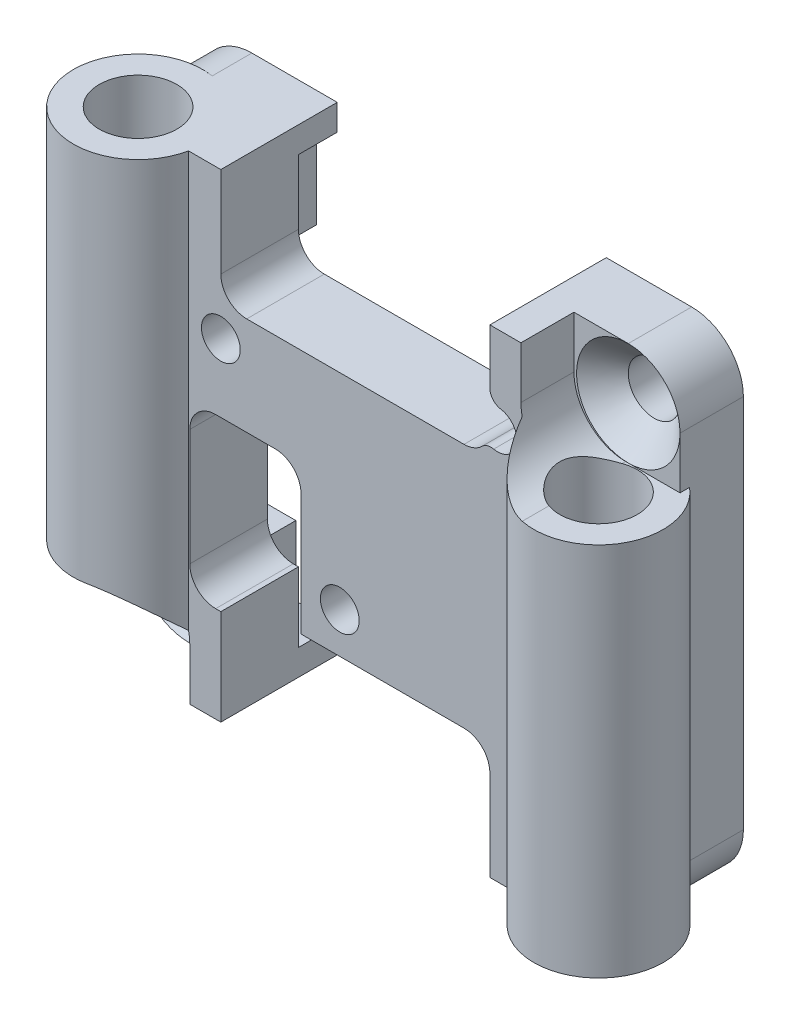
SolidWorks part; units mm, degrees
ref_plane "Top Plane" through (0, 0, 0) normal (0, 0, 1) x (1, 0, 0)
ref_plane "Right Plane" through (0, 0, 0) normal (0, 1, 0) x (1, 0, 0)
ref_plane "Front Plane" through (0, 0, 0) normal (1, 0, 0) x (0, 0, -1)
sketch "Sketch1" plane through (0, 0, 0) normal (0, 0, 1) x (1, 0, 0)
  line L1 (2, 0) -> (5.3, 0)
  line L2 (0, 2) -> (0, 16.5)
  line L3 (2, 18.5) -> (5.3, 18.5)
  line L4 (21, 2) -> (21, 16.5)
  line L5 (20, 2) -> (20, 16.5) construction
  line L6 (1, 3.7) -> (1, 14)
  line L7 (4.5, 17.5) -> (5.3, 17.5)
  line L8 (20, 2) -> (20, 14)
  line L9 (3.7, 1) -> (5.3, 1)
  line L10 (5.3, 0) -> (5.3, 1)
  line L11 (5.3, 17.5) -> (5.3, 18.5)
  line L12 (15.7, 0) -> (15.7, 1)
  line L13 (16.5, 17.5) -> (16.5, 14)
  line L14 (15.7, 17.5) -> (15.7, 18.5)
  line L15 (16.5, 14) -> (20, 14)
  line L16 (1, 3.7) -> (3.7, 3.7)
  line L17 (3.7, 3.7) -> (3.7, 1)
  line L18 (1, 14) -> (4.5, 14)
  line L19 (4.5, 14) -> (4.5, 17.5)
  line L20 (15.7, 18.5) -> (19, 18.5)
  line L21 (15.7, 17.5) -> (16.5, 17.5)
  line L22 (5.3, 18.5) -> (15.7, 18.5) construction
  line L23 (2, 18.5) -> (19, 18.5) construction
  line L24 (15.7, 1) -> (19, 1)
  line L25 (5.3, 17.5) -> (15.7, 17.5) construction
  line L26 (2, 17.5) -> (19, 17.5) construction
  line L27 (15.7, 0) -> (19, 0)
  line L28 (5.3, 1) -> (15.7, 1) construction
  line L29 (2, 1) -> (19, 1) construction
  line L31 (5.3, 0) -> (15.7, 0) construction
  line L32 (2, 0) -> (19, 0) construction
  line L33 (1, 2) -> (1, 16.5) construction
  arc A0 (2, 0) -> (0, 2) centre (2, 2) cw
  arc A1 (19, 0) -> (21, 2) centre (19, 2) ccw
  arc A2 (19, 18.5) -> (21, 16.5) centre (19, 16.5) cw
  arc A3 (0, 16.5) -> (2, 18.5) centre (2, 16.5) cw
  arc A6 (19, 1) -> (20, 2) centre (19, 2) ccw
  arc A9 (2, 1) -> (1, 2) centre (2, 2) cw construction
  arc A10 (19, 17.5) -> (20, 16.5) centre (19, 16.5) cw construction
  arc A11 (1, 16.5) -> (2, 17.5) centre (2, 16.5) cw construction
  point P7 (0, 0)
  point P10 (21, 0)
  point P15 (0, 18.5)
  dimension "D3" = 2
  dimension "D6" = 3.5
  dimension "D1" = 18.5
  dimension "D2" = 21
  dimension "D5" = 2.7
  dimension "D7" = 10.4
  dimension "D4" = 1
extrude "Boss-Extrude1" add sketch "Sketch1" along normal blind 1.5
sketch "Sketch2" plane through (0, 0, 1.5) normal (0, 0, 1) x (1, 0, 0)
  line L0 (19, 18.5) -> (15.7, 18.5) construction
  line L1 (21, 2) -> (21, 16.5) construction
  line L2 (15.7, 0) -> (19, 0) construction
  line L3 (2, 0) -> (5.3, 0) construction
  line L4 (0, 16.5) -> (0, 2) construction
  line L5 (5.3, 18.5) -> (2, 18.5) construction
  line L6 (19, 18.5) -> (15.7, 18.5)
  line L7 (21, 2) -> (21, 16.5)
  line L8 (15.7, 0) -> (19, 0)
  line L9 (2, 0) -> (5.3, 0)
  line L10 (0, 16.5) -> (0, 2)
  line L11 (5.3, 18.5) -> (2, 18.5)
  line L12 (5.3, 18.5) -> (5.3, 14)
  line L13 (5.3, 14) -> (15.7, 14)
  line L14 (15.7, 14) -> (15.7, 18.5)
  line L15 (5.3, 0) -> (5.3, 3.7)
  line L16 (5.3, 3.7) -> (4.1, 3.7)
  line L17 (4.1, 3.7) -> (4.1, 10.2)
  line L18 (4.1, 10.2) -> (8.4, 10.2)
  line L19 (8.4, 10.2) -> (8.4, 4.5)
  line L20 (8.4, 4.5) -> (15.7, 4.5)
  line L21 (15.7, 4.5) -> (15.7, 0)
  line L22 (3.7, 3.7) -> (1, 3.7) construction
  line L24 (1, 14) -> (4.5, 14) construction
  arc A0 (21, 16.5) -> (19, 18.5) centre (19, 16.5) ccw construction
  arc A1 (19, 0) -> (21, 2) centre (19, 2) ccw construction
  arc A2 (0, 2) -> (2, 0) centre (2, 2) ccw construction
  arc A3 (2, 18.5) -> (0, 16.5) centre (2, 16.5) ccw construction
  arc A4 (21, 16.5) -> (19, 18.5) centre (19, 16.5) ccw
  arc A5 (19, 0) -> (21, 2) centre (19, 2) ccw
  arc A6 (0, 2) -> (2, 0) centre (2, 2) ccw
  arc A7 (2, 18.5) -> (0, 16.5) centre (2, 16.5) ccw
  dimension "D1" = 4.3
  dimension "D2" = 1.2
  dimension "D3" = 6.5
extrude "Boss-Extrude2" add sketch "Sketch2" along normal blind 3
fillet "Fillet1" radius 1 6 edges at (5.3, 14, 3) (15.7, 14, 3) (15.7, 4.5, 3) (8.4, 10.2, 3) (4.1, 10.2, 3) (4.1, 3.7, 3)
sketch "Sketch3" plane through (0, 0, 4.5) normal (0, 0, 1) x (1, 0, 0)
  circle A0 centre (9.8986, 6.0657) radius 0.75
  circle A1 centre (5.3005, 12.837) radius 0.75
  circle A2 centre (16, 15.15) radius 0.75
  point P6 (0, 0)
  point P7 (5.5, 13.183)
  point P8 (16, 15.15)
  point P10 (5.5, 13.05)
  point P12 (9.4, 5.91)
  point P14 (0, 0)
  point P15 (5.3005, 12.837)
  point P16 (9.8986, 6.0657)
  dimension "D1" = 1.5
extrude "Cut-Extrude2" cut sketch "Sketch3" against normal through all
fillet "Fillet2" radius 0.5 2 edges at (15.5814, 14.5277, 3) (15.7, 15.8374, 3)
sketch "Sketch4" plane through (0, 0, 0) normal (0, -1, 0) x (1, 0, 0)
  line L0 (4.1, 1.5) -> (4.1, 4.5) construction
  line L1 (1.6, 4) -> (1.6, 0) construction
  line L2 (0, 0) -> (2, 0) construction
  line L3 (1.6, 0) -> (2, 0) construction
  line L6 (3.7, 1.5) -> (1, 1.5) construction
  circle A0 centre (1.6, 4) radius 2.5
  circle A1 centre (1.6, 4) radius 1.5
  line M5 (5.3, 4.5) -> (2, 4.5)
  line M6 (2, 4.5) -> (2, 0)
  dimension "D1" = 1
  dimension "D2" = 3
extrude "Boss-Extrude3" add sketch "Sketch4" against normal up to surface (18.5 mm away) up to face at (3.65, 18.5, 2.25)
extrude "Cut-Extrude3" cut sketch "Sketch4<2>" against normal through all contours A1 M6 M5 | A1 M5 M6 region at (1.3184, 0, 4.1033) region at (2.4822, 0, 3.6764)
sketch "Sketch4<2>" plane through (0, 0, 0) normal (0, -1, 0) x (1, 0, 0) same geometry as "Sketch4"
ref_plane "Plane1" through (10.5, 0, 0) normal (-1, 0, 0) x (0, 0, 1)
ref_plane "Plane2" through (0, 9.25, 0) normal (0, -1, 0) x (-1, 0, 0)
ref_axis "Axis1" through (10.5, 9.25, 6.825) along (0, 0, -1)
mirror "Mirror1" about plane through (10.5, 0, 0) normal (-1, 0, 0) of "Cut-Extrude3", "Boss-Extrude3"
sketch "Sketch6" plane through (0, 18.5, 0) normal (0, 1, 0) x (1, 0, 0)
  line L0 (21.9, -2.45) -> (16.9, -2.45)
  line L1 (21.9, -2.45) -> (21.9, -4)
  line L2 (19, 0) -> (15.7, 0) construction
  line L3 (16.9, -2.45) -> (16.9, -4.5)
  line L5 (16.9505, -4.5) -> (15.7, -4.5) construction
  line L6 (16.9, -4.5) -> (17.0923, -4.9615)
  arc A0 (17.0923, -4.9615) -> (21.9, -4) centre (19.4, -4) ccw
  arc A1 (16.9505, -4.5) -> (19, -1.5322) centre (19.4, -4) ccw construction
  dimension "D1" = 2.45
extrude "Cut-Extrude5" cut sketch "Sketch6" against normal blind 4
sketch "Sketch7" plane through (0, 0, 2.45) normal (0, 0, 1) x (1, 0, 0)
  line L0 (21, 14.5) -> (21, 16.5)
  line L1 (19, 18.5) -> (16.9, 18.5)
  line L2 (16.9, 14.5) -> (16.9, 18.5) construction
  line L3 (21.3615, 14.5) -> (16.9, 14.5) construction
  line L4 (21, 14.5) -> (22, 14.5)
  line L5 (22, 14.5) -> (22, 19.5)
  line L6 (22, 19.5) -> (16.9, 19.5)
  line L7 (16.9, 19.5) -> (16.9, 18.5)
  circle A0 centre (19, 16.5) radius 1
  arc A2 (21, 16.5) -> (19, 18.5) centre (19, 16.5) ccw construction
  arc A3 (21, 16.5) -> (19, 18.5) centre (19, 16.5) ccw
  dimension "D1" = 2
  dimension "D2" = 1
extrude "Cut-Extrude6" cut sketch "Sketch7" against normal through all both and the other way through all
chamfer "Chamfer1" distance 1 angle 45 1 edges at (18, 16.5, 2.45)
pattern_circular "CirPattern1" count 2 over 360 about axis through (10.5, 9.25, 6.825) along (0, 0, -1) of "Cut-Extrude5", "Cut-Extrude6", "Chamfer1"
fillet "Fillet3" radius 2 2 edges at (4.1, 4, 3.475) (16.9, 14.5, 3.475)
